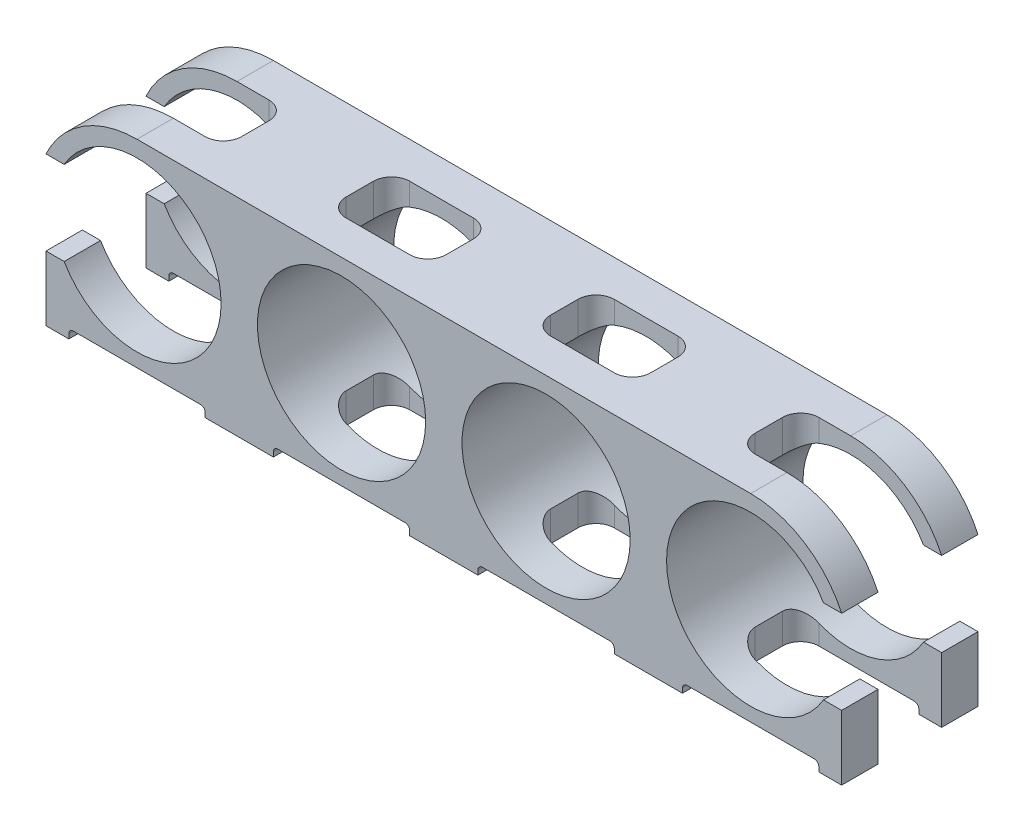
SolidWorks part; units mm, degrees
ref_plane "Front Plane" through (0, 0, 0) normal (0, 0, 1) x (1, 0, 0)
ref_plane "Top Plane" through (0, 0, 0) normal (0, 1, 0) x (1, 0, 0)
ref_plane "Right Plane" through (0, 0, 0) normal (1, 0, 0) x (0, 0, -1)
sketch "Sketch1" plane through (0, 0, 0) normal (0, 0, 1) x (1, 0, 0)
  line L0 (-41.7607, -4.625) -> (-43.7607, -4.625)
  line L1 (-41.7607, 4.625) -> (-43.7607, 4.625)
  line L2 (-33.75, 11.0275) -> (33.75, 11.0275)
  line L3 (-43.7607, -11.75) -> (43.7607, -11.75)
  line L4 (41.7607, 4.625) -> (43.7607, 4.625)
  line L5 (41.7607, -4.625) -> (43.7607, -4.625)
  line L7 (-43.7607, -11.75) -> (-43.7607, -4.625)
  line L8 (43.7607, -4.625) -> (43.7607, -11.75)
  circle A0 centre (-11.25, 0) radius 9.25 construction
  circle A1 centre (11.25, 0) radius 9.25 construction
  circle A2 centre (-33.75, 0) radius 9.25 construction
  circle A3 centre (33.75, 0) radius 9.25 construction
  arc A4 (-41.7607, 4.625) -> (-33.75, 9.25) centre (-33.75, 0) cw
  arc A5 (-43.7607, 4.625) -> (-33.75, 11.0275) centre (-33.75, 0) cw
  arc A6 (-33.75, 9.25) -> (-33.75, -9.25) centre (-33.75, 0) cw
  arc A7 (-33.75, -9.25) -> (-41.7607, -4.625) centre (-33.75, 0) cw
  circle A9 centre (-11.25, 0) radius 9.25
  circle A10 centre (11.25, 0) radius 9.25
  arc A12 (33.75, 11.0275) -> (43.7607, 4.625) centre (33.75, 0) cw
  arc A14 (33.75, 9.25) -> (41.7607, 4.625) centre (33.75, 0) cw
  arc A15 (41.7607, -4.625) -> (33.75, -9.25) centre (33.75, 0) cw
  arc A16 (33.75, 9.25) -> (33.75, -9.25) centre (33.75, 0) ccw
  point P30 (-43.7607, -8.1875)
  dimension "D5" = 18.5
  dimension "D6" = 60
  dimension "D8" = 2.5
  dimension "D1" = 22.5
  dimension "D2" = 11.25
  dimension "D3" = 22.5
  dimension "D4" = 22.5
  dimension "D7" = 2
extrude "Boss-Extrude1" add sketch "Sketch1" along normal blind 15
sketch "Sketch2" plane through (0, 11.0275, 0) normal (0, 1, 0) x (1, 0, 0)
  line L0 (0, 0) -> (0, -15) construction
  line L17 (30.25, -4) -> (46.25, -4)
  line L18 (-30.25, -9) -> (-46.25, -6) construction
  line L23 (-30.25, -6) -> (-46.25, -9) construction
  line L24 (-7.75, -9) -> (-14.75, -6) construction
  line L25 (33.75, -15) -> (-33.75, -15) construction
  line L27 (-7.75, -6) -> (-14.75, -9) construction
  line L33 (-48.25, -6) -> (-48.25, -9)
  line L34 (-30.25, -11) -> (-46.25, -11)
  line L35 (7.75, -4) -> (14.75, -4)
  line L36 (5.75, -6) -> (5.75, -9)
  line L37 (7.75, -11) -> (14.75, -11)
  line L38 (16.75, -6) -> (16.75, -9)
  line L39 (7.75, -6) -> (14.75, -9) construction
  line L40 (7.75, -9) -> (14.75, -6) construction
  line L41 (-28.25, -6) -> (-28.25, -9)
  line L42 (28.25, -6) -> (28.25, -9)
  line L43 (30.25, -11) -> (46.25, -11)
  line L44 (48.25, -6) -> (48.25, -9)
  line L45 (30.25, -6) -> (46.25, -9) construction
  line L46 (30.25, -9) -> (46.25, -6) construction
  line L47 (-16.75, -6) -> (-16.75, -9)
  line L48 (-7.75, -11) -> (-14.75, -11)
  line L49 (-5.75, -6) -> (-5.75, -9)
  line L50 (-7.75, -4) -> (-14.75, -4)
  line L51 (-30.25, -4) -> (-46.25, -4)
  arc A4 (16.75, -6) -> (14.75, -4) centre (14.75, -6) ccw
  arc A5 (7.75, -4) -> (5.75, -6) centre (7.75, -6) ccw
  arc A6 (5.75, -9) -> (7.75, -11) centre (7.75, -9) ccw
  arc A7 (14.75, -11) -> (16.75, -9) centre (14.75, -9) ccw
  arc A8 (48.25, -6) -> (46.25, -4) centre (46.25, -6) ccw
  arc A9 (30.25, -4) -> (28.25, -6) centre (30.25, -6) ccw
  arc A10 (28.25, -9) -> (30.25, -11) centre (30.25, -9) ccw
  arc A11 (46.25, -11) -> (48.25, -9) centre (46.25, -9) ccw
  arc A12 (-46.25, -11) -> (-48.25, -9) centre (-46.25, -9) cw
  arc A13 (-28.25, -9) -> (-30.25, -11) centre (-30.25, -9) cw
  arc A14 (-30.25, -4) -> (-28.25, -6) centre (-30.25, -6) cw
  arc A15 (-48.25, -6) -> (-46.25, -4) centre (-46.25, -6) cw
  arc A16 (-14.75, -11) -> (-16.75, -9) centre (-14.75, -9) cw
  arc A17 (-5.75, -9) -> (-7.75, -11) centre (-7.75, -9) cw
  arc A18 (-7.75, -4) -> (-5.75, -6) centre (-7.75, -6) cw
  arc A19 (-16.75, -6) -> (-14.75, -4) centre (-14.75, -6) cw
  point P0 (11.25, -7.5)
  point P6 (38.25, -7.5)
  point P20 (0, -7.5)
  dimension "D10" = 2
  dimension "D17" = 2
  dimension "D12" = 7
  dimension "D13" = 11
  dimension "D14" = 11.25
  dimension "D19" = 20
  dimension "D20" = 11.5
  dimension "D21" = 7
  dimension "D8" = 90
  dimension "D9" = 90
  dimension "D11" = 90
  dimension "D15" = 90
  dimension "D16" = 90
  dimension "D18" = 90
extrude "Cut-Extrude1" cut sketch "Sketch2" against normal up to surface (22.7775 mm away) up to face at (0, -11.75, 7.5)
sketch "Sketch3" plane through (0, -11.75, 0) normal (0, -1, 0) x (1, 0, 0)
  line L0 (0, 15) -> (0, 0) construction
  line L1 (-43.7607, 15) -> (43.7607, 15) construction
  line L2 (-43.7607, 0) -> (43.7607, 0) construction
  line L3 (-28.25, 7.5) -> (-16.75, 7.5) construction
  line L4 (-28.25, 6) -> (-28.25, 9) construction
  line L5 (-16.75, 9) -> (-16.75, 6) construction
  line L6 (16.75, 7.5) -> (28.25, 7.5) construction
  line L7 (16.75, 6) -> (16.75, 9) construction
  line L8 (28.25, 9) -> (28.25, 6) construction
  circle A0 centre (0, 7.5) radius 1.325
  circle A1 centre (-22.5, 7.5) radius 1.325
  circle A2 centre (22.5, 7.5) radius 1.325
  point P13 (0, 7.5)
  point P20 (-22.5, 7.5)
  point P21 (22.5, 7.5)
  dimension "D1" = 2.65
extrude "Cut-Extrude2" cut sketch "Sketch3" against normal blind 7
thread "Thread1" pitch 0.5 method cut profile "Thread Profile1" start angle 0, offset 0, length 0, pitch 0.5, diameter 2.65
ref_plane "Plane1" through (-21.175, -11.75, 7.5) normal (0, 0, 1) x (1, 0, 0)
sketch "Thread Profile1" plane through (-21.175, -11.75, 7.5) normal (0, 0, 1) x (1, 0, 0)
  line L0 (0, 0) -> (0, 0.5) construction
  line L1 (0, 0) -> (0.2706, 0.1562)
  line L2 (0.2706, 0.1562) -> (0.2706, 0.2187)
  line L3 (0.2706, 0.2187) -> (0, 0.375)
  line L4 (0.2706, 0.1875) -> (0, 0.1875) construction
  line L11 (0, 0) -> (0, 0.375)
  point P2 (0, 0)
  dimension "Pitch" = 0.5
  dimension "Profile_Angle" = 60
  dimension "Profile_Land" = 0.0625
  dimension "Profile_Height" = 0.2706
thread "Thread2" pitch 0.5 method cut profile "Thread Profile2" start angle 0, offset 0, length 0, pitch 0.5, diameter 2.65
ref_plane "Plane2" through (1.325, -11.75, 7.5) normal (0, 0, 1) x (1, 0, 0)
sketch "Thread Profile2" plane through (1.325, -11.75, 7.5) normal (0, 0, 1) x (1, 0, 0)
  line L0 (0, 0) -> (0, 0.5) construction
  line L1 (0, 0) -> (0.2706, 0.1562)
  line L2 (0.2706, 0.1562) -> (0.2706, 0.2187)
  line L3 (0.2706, 0.2187) -> (0, 0.375)
  line L4 (0.2706, 0.1875) -> (0, 0.1875) construction
  line L11 (0, 0) -> (0, 0.375)
  point P2 (0, 0)
  dimension "Pitch" = 0.5
  dimension "Profile_Angle" = 60
  dimension "Profile_Land" = 0.0625
  dimension "Profile_Height" = 0.2706
thread "Thread3" pitch 0.5 method cut profile "Thread Profile3" start angle 0, offset 0, length 0, pitch 0.5, diameter 2.65
ref_plane "Plane3" through (23.825, -11.75, 7.5) normal (0, 0, 1) x (1, 0, 0)
sketch "Thread Profile3" plane through (23.825, -11.75, 7.5) normal (0, 0, 1) x (1, 0, 0)
  line L0 (0, 0) -> (0, 0.5) construction
  line L1 (0, 0) -> (0.2706, 0.1562)
  line L2 (0.2706, 0.1562) -> (0.2706, 0.2187)
  line L3 (0.2706, 0.2187) -> (0, 0.375)
  line L4 (0.2706, 0.1875) -> (0, 0.1875) construction
  line L11 (0, 0) -> (0, 0.375)
  point P2 (0, 0)
  dimension "Pitch" = 0.5
  dimension "Profile_Angle" = 60
  dimension "Profile_Land" = 0.0625
  dimension "Profile_Height" = 0.2706
sketch "Sketch4" plane through (0, 0, 15) normal (0, 0, 1) x (1, 0, 0)
  line L0 (-20.5, 0) -> (-2, 0) construction
  line L1 (-43.7607, -11.75) -> (43.7607, -11.75) construction
  line L2 (-18.25, -10.75) -> (-4.25, -10.75)
  line L3 (-18.75, -11.25) -> (-18.75, -11.75)
  line L4 (-18.75, -11.75) -> (-3.75, -11.75)
  line L5 (-3.75, -11.25) -> (-3.75, -11.75)
  line L6 (-18.75, -10.75) -> (-3.75, -11.75) construction
  line L7 (-18.75, -11.75) -> (-3.75, -10.75) construction
  line L8 (0, 11.0275) -> (0, -11.75) construction
  line L9 (33.75, 11.0275) -> (-33.75, 11.0275) construction
  line L10 (-20.5, 0) -> (-24.5, 0) construction
  line L11 (-22.5, 11.0275) -> (-22.5, 0) construction
  line L12 (-26.25, -11.75) -> (-41.25, -10.75) construction
  line L13 (-26.25, -10.75) -> (-41.25, -11.75) construction
  line L14 (-41.25, -11.25) -> (-41.25, -11.75)
  line L15 (-26.25, -11.75) -> (-41.25, -11.75)
  line L16 (-26.25, -11.25) -> (-26.25, -11.75)
  line L17 (-26.75, -10.75) -> (-40.75, -10.75)
  line L18 (26.25, -10.75) -> (41.25, -11.75) construction
  line L19 (26.25, -11.75) -> (41.25, -10.75) construction
  line L20 (18.75, -11.75) -> (3.75, -10.75) construction
  line L21 (18.75, -10.75) -> (3.75, -11.75) construction
  line L22 (26.75, -10.75) -> (40.75, -10.75)
  line L23 (26.25, -11.25) -> (26.25, -11.75)
  line L24 (26.25, -11.75) -> (41.25, -11.75)
  line L25 (41.25, -11.25) -> (41.25, -11.75)
  line L26 (3.75, -11.25) -> (3.75, -11.75)
  line L27 (18.75, -11.75) -> (3.75, -11.75)
  line L28 (18.75, -11.25) -> (18.75, -11.75)
  line L29 (18.25, -10.75) -> (4.25, -10.75)
  circle A0 centre (-11.25, 0) radius 9.25 construction
  arc A1 (-4.25, -10.75) -> (-3.75, -11.25) centre (-4.25, -11.25) cw
  arc A2 (-18.25, -10.75) -> (-18.75, -11.25) centre (-18.25, -11.25) ccw
  arc A3 (-41.7607, -4.625) -> (-41.7607, 4.625) centre (-33.75, 0) ccw construction
  arc A4 (-26.75, -10.75) -> (-26.25, -11.25) centre (-26.75, -11.25) cw
  arc A5 (-40.75, -10.75) -> (-41.25, -11.25) centre (-40.75, -11.25) ccw
  arc A6 (40.75, -10.75) -> (41.25, -11.25) centre (40.75, -11.25) cw
  arc A7 (26.75, -10.75) -> (26.25, -11.25) centre (26.75, -11.25) ccw
  arc A8 (18.25, -10.75) -> (18.75, -11.25) centre (18.25, -11.25) cw
  arc A9 (4.25, -10.75) -> (3.75, -11.25) centre (4.25, -11.25) ccw
  point P5 (-11.25, -11.25)
  point P13 (-11.25, 0)
  point P39 (-33.75, -11.25)
  point P60 (33.75, -11.25)
  point P61 (11.25, -11.25)
  dimension "D3" = 0.5
  dimension "D1" = 1
  dimension "D2" = 15
extrude "Cut-Extrude3" cut sketch "Sketch4" against normal up to surface (15 mm away) up to face at (20.5, 0, 0)
